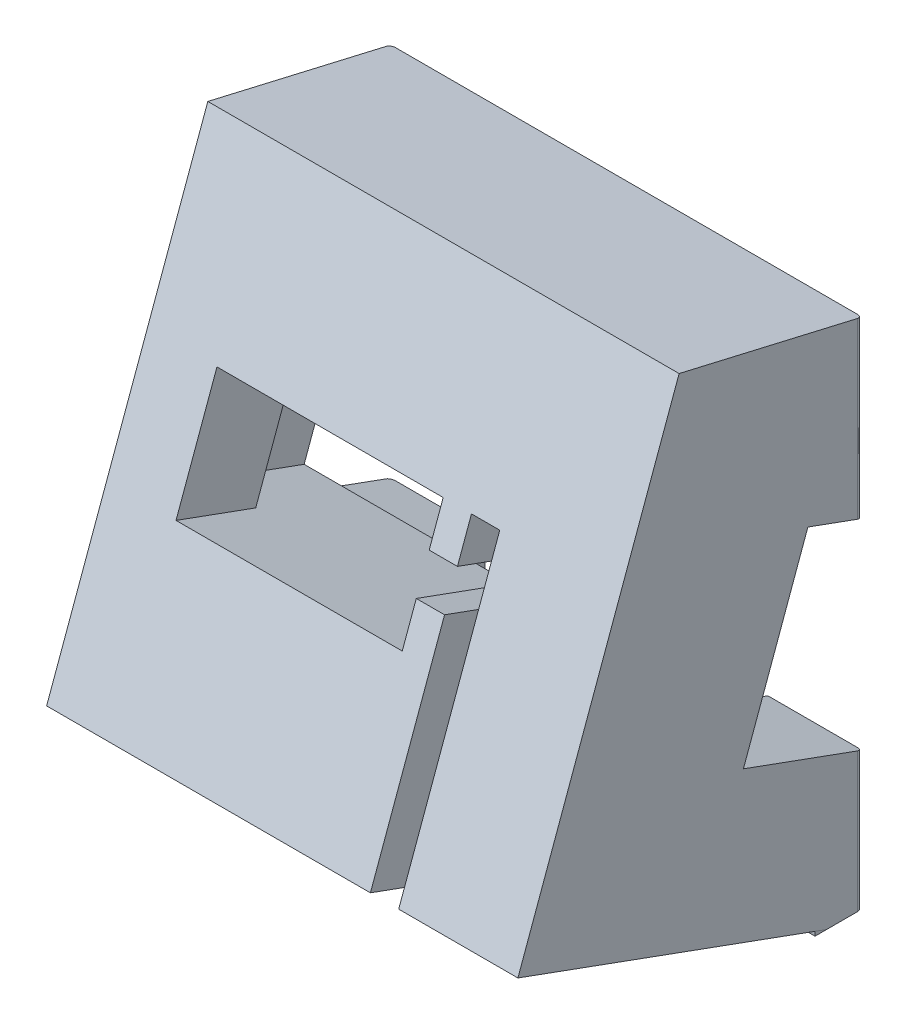
SolidWorks part; units mm, degrees
ref_plane "Front Plane" through (0, 0, 0) normal (0, 0, 1) x (1, 0, 0)
ref_plane "Top Plane" through (0, 0, 0) normal (0, 1, 0) x (1, 0, 0)
ref_plane "Right Plane" through (0, 0, 0) normal (1, 0, 0) x (0, 0, -1)
sketch "Sketch2" plane through (0, 0, 0) normal (0, 0, 1) x (1, 0, 0)
  line L0 (-100, -75) -> (-100, -45)
  line L1 (-100, 75) -> (100, 75)
  line L2 (-100, 75) -> (-100, -75)
  line L3 (-100, -75) -> (100, -75)
  line L4 (100, 75) -> (100, -75)
  line L5 (-100, 75) -> (100, -75) construction
  line L6 (-100, -75) -> (100, 75) construction
  line L7 (-100, -45) -> (-60, -45)
  line L8 (-60, -45) -> (-60, -75)
  line L9 (100, -75) -> (100, -45)
  line L10 (100, -45) -> (60, -45)
  line L11 (60, -45) -> (60, -75)
  line L12 (-60, -75) -> (-60, -65)
  line L13 (-60, -65) -> (60, -65)
  line L14 (-60, -45) -> (-50, -45)
  line L15 (-50, -45) -> (-50, -55)
  line L16 (-50, -55) -> (-60, -55)
  line L17 (60, -45) -> (50, -45)
  line L18 (50, -45) -> (50, -55)
  line L19 (50, -55) -> (60, -55)
  line L20 (-55, -55) -> (-55, -50)
  line L21 (-55, -50) -> (-50, -50)
  line L22 (-50, -45) -> (-52, -45)
  line L23 (-50, -45) -> (-50, -47)
  line L24 (0, -65) -> (0, -61.3332)
  line L25 (-58, -53) -> (-52, -53)
  line L26 (-58, -53) -> (-58, -47)
  line L27 (-58, -47) -> (-52, -47)
  line L28 (-52, -53) -> (-52, -47)
  line L29 (-58, -53) -> (-52, -47) construction
  line L30 (-58, -47) -> (-52, -53) construction
  line L31 (58, -47) -> (52, -47)
  line L32 (52, -53) -> (52, -47)
  line L33 (58, -53) -> (52, -53)
  line L34 (58, -53) -> (58, -47)
  point P0 (0, 0)
  dimension "D1" = 200
  dimension "D2" = 150
  dimension "D3" = 40
extrude "Boss-Extrude1" add sketch "Sketch2" along normal blind 5 contours L19 L18 L17 L10 L4 L1 L2 L7 L14 L15 L16 L8 L13 L11 | L18 L19 L11 L17 L34 L33 L32 L31 | L28 L21 L15 L14 L8 L16 L20 L25 L26 L27 | L28 L25 L20 L16 L15 L21 region at (0, 9.084, 0) region at (-56, -45.1414, 0) region at (-51.9375, -53.0625, 0) region at (55, -54.8586, 0)
sketch "Sketch3" plane through (0, 0, 5) normal (0, 0, 1) x (1, 0, 0)
  line L0 (-100, 75) -> (-100, -45) construction
  line L1 (-100, 75) -> (-100, 55)
  line L2 (-100, 55) -> (100, 55)
  line L3 (100, 75) -> (100, -45) construction
  line L4 (100, 55) -> (100, 75)
  line L5 (100, 75) -> (-100, 75)
extrude "Cut-Extrude1" cut sketch "Sketch3" against normal blind 5
sketch "Sketch4" plane through (0, 0, 0) normal (0, 0, -1) x (-1, 0, 0)
  line L0 (-100, 55) -> (100, 55)
  line L1 (100, 55) -> (100, -45)
  line L2 (100, -45) -> (-100, -45)
  line L3 (-100, -45) -> (-100, 55)
  line L4 (100, 55) -> (95, 55)
  line L5 (95, 55) -> (95, -45)
  line L6 (95, -45) -> (100, -45)
  line L7 (100, 55) -> (100, 45)
  line L8 (100, 45) -> (95, 45)
  line L9 (95, 45) -> (95, 50)
  line L10 (95, 50) -> (100, 50)
  line L11 (100, 50) -> (99, 50)
  line L12 (100, 50) -> (100, 49)
  line L13 (97.5, 45) -> (97.5, 47.5)
  line L14 (100, 5) -> (95, 5)
  line L15 (96, 46) -> (99, 46)
  line L16 (96, 46) -> (96, 49)
  line L17 (96, 49) -> (99, 49)
  line L18 (99, 46) -> (99, 49)
  line L19 (96, 46) -> (99, 49) construction
  line L20 (96, 49) -> (99, 46) construction
  line L21 (96, -39) -> (99, -39)
  line L22 (99, -36) -> (99, -39)
  line L23 (96, -36) -> (99, -36)
  line L24 (96, -36) -> (96, -39)
  line L25 (100, 5) -> (100, 7.5)
  line L26 (100, 5) -> (100, 2.5)
  line L27 (100, 2.5) -> (95, 2.5)
  line L28 (95, 2.5) -> (95, 7.5)
  line L29 (95, 7.5) -> (100, 7.5)
  line L30 (100, 2.5) -> (99, 2.5)
  line L31 (100, 2.5) -> (100, 3.5)
  line L32 (0, -45) -> (0, -36)
  line L33 (96, 6.5) -> (99, 6.5)
  line L34 (96, 6.5) -> (96, 3.5)
  line L35 (96, 3.5) -> (99, 3.5)
  line L36 (99, 6.5) -> (99, 3.5)
  line L37 (96, 6.5) -> (99, 3.5) construction
  line L38 (96, 3.5) -> (99, 6.5) construction
  line L39 (97.5, -36) -> (97.5, -39)
  line L40 (100, 50) -> (95, 50)
  line L41 (100, 50) -> (100, 45)
  line L42 (100, 45) -> (95, 45)
  line L43 (95, 50) -> (95, 45)
  line L44 (100, 50) -> (95, 45) construction
  line L45 (100, 45) -> (95, 50) construction
  line L46 (97.5, -39) -> (97.5, -40)
  line L47 (-100, 45) -> (-95, 45)
  line L48 (100, -35) -> (95, -35)
  line L49 (100, -35) -> (100, -40)
  line L50 (100, -40) -> (95, -40)
  line L51 (95, -35) -> (95, -40)
  line L52 (100, -35) -> (95, -40) construction
  line L53 (100, -40) -> (95, -35) construction
  line L54 (-95, 50) -> (-95, 45)
  line L55 (-100, 50) -> (-95, 50)
  line L56 (-100, 50) -> (-100, 45)
  line L57 (-100, 5) -> (-100, 7.5)
  line L58 (-95, 7.5) -> (-100, 7.5)
  line L59 (-95, 2.5) -> (-95, 7.5)
  line L60 (-100, 2.5) -> (-95, 2.5)
  line L61 (-100, 5) -> (-100, 2.5)
  line L62 (-100, -40) -> (-95, -40)
  line L63 (-95, -35) -> (-95, -40)
  line L64 (-100, -35) -> (-95, -35)
  line L65 (-100, -35) -> (-100, -40)
  point P31 (97.5, 5)
  point P44 (97.5, -37.5)
  line M38 (-100, 55) -> (-100, -45)
extrude "Cut-Extrude2" cut sketch "Sketch4" against normal blind 5 contours L55 L3 L47 L54 | L3 L60 L59 L58 M38 | L64 L3 L62 L63 | L18 L15 L8 L1 L7 L10 L5 L16 L17 | L15 L18 L17 L16 | L33 L36 L14 L1 L29 L5 L34 | L14 L36 L35 L34 L5 L27 L1 L26 | L36 L14 L34 L35 | L36 L33 L34 L14 | L50 L1 L48 L5 L21 L24 L23 L22 | L23 L39 L21 L22 | L39 L23 L24 L21 region at (97.5, 47.5, 0) region at (-96.75, 46.0424, 0) region at (-97, 49.9293, 0) region at (97.5, 5, 0) region at (-97.5, 6.5313, 0) region at (-97.5, 3.4688, 0) region at (-97.5, 5.75, 0) region at (-97.5, 4.25, 0) region at (97.5, -37.5, 0) region at (-96.75, -37.5, 0) region at (-98.25, -37.5, 0) region at (-97.5, -35.0707, 0)
sketch "Sketch6" plane through (0, 0, 0) normal (0, 0, -1) x (-1, 0, 0)
  line L0 (0, -65) -> (0, -45)
  line L1 (60, -65) -> (-60, -65) construction
  line L2 (0, -45) -> (50, -45)
  line L3 (50, -45) -> (50, -65)
  line L4 (0, -45) -> (-50, -45)
  line L5 (-50, -45) -> (-50, -65)
  line L6 (-50, -45) -> (-60, -45)
  line M21 (-60, -65) -> (60, -65)
extrude "Boss-Extrude2" add sketch "Sketch6" along normal blind 100 contours L3 L2 L0 M21 | L4 L5 L0 M21 region at (25, -55, 0) region at (-25, -55, 0)
sketch "Sketch8" plane through (50, 0, 0) normal (1, 0, 0) x (0, 0, -1)
  line L0 (100, -45) -> (100, 55)
  line L1 (100, 55) -> (78.5761, 55)
  line L2 (100, -45) -> (42.1791, -45)
  line L3 (100, -45) -> (0, -45) construction
  line L4 (78.5761, 55) -> (42.1791, -45)
  line L5 (60.3776, 5) -> (63.7978, 14.3969)
  line L6 (60.3776, 5) -> (56.9574, -4.3969)
  line M8 (100, -45) -> (0, -45)
  dimension "D1" = 21.4239
  dimension "D2" = 57.8209
extrude "Boss-Extrude3" add sketch "Sketch8" against normal blind 100 contours L1 L4 L0 M8 region at (50, -2.655, -78.7957)
sketch "Sketch12" plane through (50, 0, 0) normal (1, 0, 0) x (0, 0, -1)
  line L0 (42.1791, -45) -> (78.5761, 55)
  line L2 (42.1791, -45) -> (100, -45)
  line L3 (100, 55) -> (100, -65) construction
  line L4 (100, -45) -> (100, 55)
  line L5 (78.5761, 55) -> (83.897, 55)
  line L6 (100, 55) -> (78.5761, 55) construction
  line L7 (83.897, 55) -> (88.897, 55)
  line L8 (83.897, 55) -> (47.5, -45)
  line L9 (88.897, 55) -> (52.5, -45)
  line M5 (100, 55) -> (78.5761, 55)
  line M6 (78.5761, 55) -> (42.1791, -45)
  dimension "D1" = 5.3209
extrude "Cut-Extrude4" cut sketch "Sketch12" against normal blind 100 contours L8 L2 M5 M6 region at (50, 5, -63.0381)
sketch "Sketch13" plane through (0, -20.5302, -56.4063) normal (0, 0.342, 0.9397) x (1, 0, 0)
  line L0 (-50, 80.3776) -> (50, 80.3776)
  line L1 (50, 80.3776) -> (50, -26.0402)
  line L2 (50, -26.0402) -> (-50, -26.0402)
  line L3 (-50, -26.0402) -> (-50, 80.3776)
  line L4 (0, 80.3776) -> (0, 27.1687)
  circle A0 centre (0, 27.1687) radius 10
extrude "Boss-Extrude5" add sketch "Sketch13" along normal blind 100 contours A0 region at (6.8711, 11.4567, -68.0486)
sketch "Sketch14" plane through (0, 13.6718, 37.563) normal (0, 0.342, 0.9397) x (1, 0, 0)
  circle A0 centre (0, 27.1687) radius 10.3
  circle A1 centre (0, 27.1687) radius 12.5
  circle M3 centre (0, 27.1687) radius 10
  dimension "D1" = 25
extrude "Cut-Extrude5" cut sketch "Sketch14" against normal blind 100 contours M3 | A1 M3 | A0 M3 | A0 | A1 region at (-10.0087, 39.202, 28.2708) region at (-12.1464, 39.202, 28.2708) region at (0, 39.202, 28.2708)
ref_plane "Plane1" through (0, 13.6718, 37.563) normal (0, 0.342, 0.9397) x (1, 0, 0)
sketch "Sketch15" plane through (0, 13.6718, 37.563) normal (0, 0.342, 0.9397) x (1, 0, 0)
  circle A0 centre (0, 27.1687) radius 10
  circle A1 centre (0, 27.1687) radius 12.5
  circle A2 centre (0, 27.1687) radius 15
ref_plane "Plane2" through (0, 0, -30) normal (0, 0, -1) x (-1, 0, 0)
extrude "Boss-Extrude6" add sketch "Sketch15" against normal blind 40 contours A2 A1 region at (-14.5757, 39.202, 28.2708)
sketch "Sketch16" plane through (0, 0, -30) normal (0, 0, -1) x (-1, 0, 0)
  line L0 (0, 61.0723) -> (0, 0)
  line L1 (0, 0) -> (25, 0)
  line L2 (25, 0) -> (25, 61.0723)
  line L3 (25, 61.0723) -> (-25, 61.0723)
  line L4 (-25, 61.0723) -> (-25, 0)
  line L5 (-25, 0) -> (0, 0)
sketch "Sketch17" plane through (0, 13.6718, 37.563) normal (0, 0.342, 0.9397) x (1, 0, 0)
  circle A0 centre (0, 27.1687) radius 10.3
  circle A1 centre (0, 27.1687) radius 12.5
extrude "Cut-Extrude10" cut sketch "Sketch16" against normal blind 35 contours L4 L5 L0 L3 | L2 L3 L0 L1 region at (-12.5, 30.5361, -30) region at (12.5, 30.5361, -30)
sketch "Sketch18" plane through (0, 0, 5) normal (0, 0, 1) x (1, 0, 0)
  line L0 (25, 55) -> (25, 0)
  line L1 (25, 0) -> (-25, 0)
  line L2 (-25, 0) -> (-25, 55)
  line L3 (-25, 55) -> (25, 55)
  line L4 (-30, 55) -> (-30, 60)
  line L5 (30, 0) -> (30, 55)
  line L6 (25, 55) -> (100, 55) construction
  line L7 (30, 55) -> (25, 55)
  line L8 (30, 0) -> (30, -5)
  line L9 (30, -5) -> (-30, -5)
  line L10 (-30, -5) -> (-30, 55)
  line L11 (-100, 55) -> (-25, 55) construction
  line L12 (-30, 55) -> (-25, 55)
  line L13 (-30, 60) -> (30, 60)
  line L14 (30, 60) -> (30, 55)
  line L15 (-30, 55) -> (30, 55)
  line M5 (25, 55) -> (25, 0)
  line M6 (25, 0) -> (-25, 0)
  line M7 (-25, 0) -> (-25, 55)
  line M8 (-25, 55) -> (-100, 55)
  line M40 (100, 55) -> (25, 55)
sketch "Sketch20" plane through (0, 0, 5) normal (0, 0, -1) x (-1, 0, 0)
  ellipse E2 centre (0, 30.7322) end of major axis (0, 44.0344) minor radius 12.5 (0, 44.0344) -> (0, 44.0344) ccw
  ellipse E3 centre (0, 30.7322) end of major axis (0, 44.0344) minor radius 12.5
  ellipse E5 centre (0, 30.7322) end of major axis (0, 46.6948) minor radius 15 (0, 46.6948) -> (0, 46.6948) ccw
  ellipse E6 centre (0, 30.7322) end of major axis (0, 46.6948) minor radius 15
  dimension "D1" = 0
  dimension "D2" = 0
sketch "Sketch21" plane through (0, 0, -30) normal (0, 0, -1) x (-1, 0, 0)
  line L0 (0, 30.7322) -> (0, 46.6948)
  line L1 (0, 46.6948) -> (-15, 46.6948)
  line L2 (-15, 46.6948) -> (-15, 14.7695)
  line L3 (-15, 14.7695) -> (15, 14.7695)
  line L4 (15, 14.7695) -> (15, 46.6948)
  line L5 (15, 46.6948) -> (0, 46.6948)
  line L6 (-25, 55) -> (-25, 0)
  line L7 (-25, 0) -> (25, 0)
  line L8 (25, 0) -> (25, 55)
  line L9 (25, 55) -> (-25, 55)
  line L10 (-30, 55) -> (-30, 60)
  line L11 (-30, 60) -> (-25, 60)
  line L12 (-25, 60) -> (30, 60)
  line L13 (30, 60) -> (30, 55)
  line L14 (30, 55) -> (30, -5)
  line L15 (30, -5) -> (-30, -5)
  line L16 (-30, -5) -> (-30, 55)
  line L17 (-25, 55) -> (-30, 55)
  line L18 (25, 55) -> (30, 55)
  line L19 (-25, 55) -> (25, 55)
  ellipse E2 centre (0, 30.7322) end of major axis (0, 46.6948) minor radius 15
  ellipse E3 centre (0, 30.7322) end of major axis (0, 46.6948) minor radius 15
  ellipse E5 centre (0, 30.7322) end of major axis (0, 44.0344) minor radius 12.5
  ellipse E6 centre (0, 30.7322) end of major axis (0, 44.0344) minor radius 12.5
  dimension "D1" = 0
  dimension "D2" = 0
extrude "Cut-Extrude11" cut sketch "Sketch15<4>" against normal blind 15 contours A2 A1 region at (-14.5757, 39.202, 28.2708)
sketch "Sketch15<4>" plane through (0, 13.6718, 37.563) normal (0, 0.342, 0.9397) x (1, 0, 0) same geometry as "Sketch15"
sketch "Sketch22" plane through (0, 0, 0) normal (0, 0, -1) x (-1, 0, 0)
  line L0 (30, -5) -> (-30, -5)
  line L1 (-30, -5) -> (-30, 60)
  line L2 (-30, 60) -> (30, 60)
  line L3 (30, 60) -> (30, -5)
  line L4 (25, 0) -> (-25, 0)
  line L5 (-25, 0) -> (-25, 55)
  line L6 (-25, 55) -> (25, 55)
  line L7 (25, 55) -> (25, 0)
  line L8 (-25, 55) -> (-30, 55)
  line L9 (-25, 55) -> (-100, 55) construction
  line L10 (25, 55) -> (30, 55)
  line L11 (30, -5) -> (30, 55) construction
  line L12 (25, 0) -> (30, 0)
  line L13 (-25, 0) -> (-30, 0)
  line M17 (25, 0) -> (-25, 0)
  line M18 (-25, 0) -> (-25, 55)
  line M56 (25, 55) -> (25, 0)
extrude "Boss-Extrude7" add sketch "Sketch18" along normal blind 5 contours L10 L9 L8 L5 M40 M5 M6 M7 M8 region at (27.5, 54.1515, 5)
sketch "Sketch23" plane through (0, 8.5415, 23.4676) normal (0, 0.342, 0.9397) x (1, 0, 0)
  circle A0 centre (0, 27.1687) radius 15
  circle A1 centre (0, 27.1687) radius 10.3
  circle A2 centre (0, 27.1687) radius 12.5
  circle M4 centre (0, 27.1687) radius 12.5
  circle M5 centre (0, 27.1687) radius 15
extrude "Boss-Extrude8" add sketch "Sketch23" against normal blind 25 contours M5 M4 region at (-14.5757, 34.0717, 14.1754)
extrude "Cut-Extrude12" cut sketch "Sketch21" against normal blind 35 contours E6 E3 | E6 | L8 L9 L6 L7 L5 L4 L3 L2 L1 | E3 L4 L5 | E3 L1 L2 | E3 L2 L3 | E3 L3 L4 region at (-10.4462, 41.5478, -30) region at (11.6495, 43.1293, -30) region at (-11.6495, 43.1293, -30) region at (0, 17.795, -30) region at (11.6495, 18.335, -30) region at (-11.6495, 18.335, -30) region at (0, 54.2567, -30)
extrude "Boss-Extrude9" add sketch "Sketch22" against normal blind 5 contours L6 M18 M17 M56 region at (0, 27.5, 0)
extrude "Cut-Extrude13" cut sketch "Sketch23<3>" against normal blind 20 contours A1 M4 | A1 region at (0, 34.0717, 14.1754) region at (-12.1464, 34.0717, 14.1754)
sketch "Sketch23<3>" plane through (0, 8.5415, 23.4676) normal (0, 0.342, 0.9397) x (1, 0, 0) same geometry as "Sketch23"
sketch "Sketch27" plane through (0, 8.5415, 23.4676) normal (0, 0.342, 0.9397) x (1, 0, 0)
  line L1 (-2, 42.1687) -> (2, 42.1687)
  line L2 (-2, 42.1687) -> (-2, 12.1687)
  line L3 (-2, 12.1687) -> (2, 12.1687)
  line L4 (2, 42.1687) -> (2, 12.1687)
  line L5 (-2, 42.1687) -> (2, 12.1687) construction
  line L6 (-2, 12.1687) -> (2, 42.1687) construction
  line L7 (-15, 29.1687) -> (15, 29.1687)
  line L8 (-15, 29.1687) -> (-15, 25.1687)
  line L9 (-15, 25.1687) -> (15, 25.1687)
  line L10 (15, 29.1687) -> (15, 25.1687)
  line L11 (-15, 29.1687) -> (15, 25.1687) construction
  line L12 (-15, 25.1687) -> (15, 29.1687) construction
  circle A0 centre (0, 27.1687) radius 12.5
  circle A1 centre (0, 27.1687) radius 15
  point P0 (0, 27.1687)
  point P6 (0, 27.1687)
  circle M8 centre (0, 27.1687) radius 12.5
  circle M9 centre (0, 27.1687) radius 15
  dimension "D1" = 4
  dimension "D2" = 4
  dimension "D3" = 30
  dimension "D4" = 30
extrude "Cut-Extrude15" cut sketch "Sketch27" against normal blind 3 contours L4 L2 M9 M8 | L9 L7 M8 M9 | L9 L7 M9 M8 | L4 L2 M8 M9 region at (0, 46.9463, 9.4894) region at (-13.7008, 34.0717, 14.1754) region at (13.7008, 34.0717, 14.1754) region at (0, 21.1972, 18.8613)
sketch "Sketch28" plane through (0, 0, 10) normal (0, 0, 1) x (1, 0, 0)
  line L0 (-25, 55) -> (-25, 5)
  line L1 (-25, 55) -> (-25, 0) construction
  line L2 (-25, 5) -> (25, 5)
  line L3 (25, 55) -> (25, 0) construction
  line L4 (25, 5) -> (25, 0)
  line L5 (25, 0) -> (-25, 0)
  line L6 (-25, 0) -> (-25, 5)
  line L7 (-25, 0) -> (-30, 0)
  line L8 (-30, -5) -> (-30, 55) construction
  line L9 (-30, 0) -> (-30, -5)
  line L10 (-30, -5) -> (30, -5)
  line L11 (30, -5) -> (30, 0)
  line L12 (30, 55) -> (30, -5) construction
  line L13 (30, 0) -> (25, 0)
  line M1 (-30, 55) -> (-30, -5)
  line M2 (-30, -5) -> (30, -5)
  line M3 (30, -5) -> (30, 55)
  line M5 (25, 55) -> (25, 0)
  line M6 (25, 0) -> (-25, 0)
  line M7 (-25, 0) -> (-25, 55)
extrude "Cut-Extrude16" cut sketch "Sketch28" against normal blind 5 contours L13 L7 M3 M6 M1 M2 region at (0, -2.5, 10)
extrude "Boss-Extrude12" add sketch "Sketch28<3>" against normal blind 5 contours L2 M7 M6 M5 region at (0, 2.5, 10)
sketch "Sketch28<3>" plane through (0, 0, 10) normal (0, 0, 1) x (1, 0, 0) same geometry as "Sketch28"
sketch "Sketch31" plane through (0, 8.5415, 23.4676) normal (0, 0.342, 0.9397) x (1, 0, 0)
  line L0 (0, 33.5187) -> (6.35, 33.5187)
  line L1 (6.35, 33.5187) -> (6.35, 27.1687)
  line L2 (6.35, 27.1687) -> (6.35, 20.8187)
  line L3 (6.35, 20.8187) -> (0, 20.8187)
  line L4 (6.35, 33.5187) -> (-17.65, 33.5187)
  line L5 (-17.65, 33.5187) -> (-17.65, 20.8187)
  line L6 (-17.65, 20.8187) -> (6.35, 20.8187)
  line L7 (-17.65, 33.5187) -> (-22.85, 33.5187)
  line L8 (-22.85, 33.5187) -> (-22.85, 20.8187)
  line L9 (-22.85, 20.8187) -> (-17.65, 20.8187)
  line L10 (6.35, 33.5187) -> (11.55, 33.5187)
  line L11 (11.55, 33.5187) -> (11.55, 20.8187)
  line L12 (11.55, 20.8187) -> (6.35, 20.8187)
  line L14 (-25, 52.1687) -> (25, 52.1687)
  line L15 (-25, 52.1687) -> (-25, 2.1687)
  line L16 (-25, 2.1687) -> (25, 2.1687)
  line L17 (25, 52.1687) -> (25, 2.1687)
  line L18 (-25, 52.1687) -> (25, 2.1687) construction
  line L19 (-25, 2.1687) -> (25, 52.1687) construction
  circle A0 centre (0, 27.1687) radius 2.5
  circle A1 centre (0, 27.1687) radius 6.35
  arc M3 (14.8661, 29.1687) -> (2, 42.0347) centre (0, 27.1687) ccw
  line M4 (2, 42.0347) -> (2, 39.5076)
  arc M5 (2, 39.5076) -> (12.339, 29.1687) centre (0, 27.1687) cw
  line M6 (12.339, 29.1687) -> (14.8661, 29.1687)
  dimension "D1" = 5
  dimension "D2" = 6.35
  dimension "D3" = 50
  dimension "D4" = 50
extrude "Boss-Extrude13" add sketch "Sketch31" along normal blind 20 contours L17 L14 L15 L16 L11 L12 L3 L6 L9 L8 L7 L4 L0 L10 M5 M4 M3 M6 | L10 L11 M5 M6 M3 M4 | L12 L11 L10 L1 L2 M5 | L11 L10 M5 | L8 L9 L5 L7 region at (8.9293, 34.0232, 14.193) region at (-20.25, 34.0717, 14.1754) region at (9.074, 42.6669, 11.047) region at (11.2964, 39.562, 12.1771) region at (0, 56.8996, 5.8667)
extrude "Cut-Extrude17" cut sketch "Sketch31<5>" along normal blind 11 contours L12 L11 L10 L1 L2 M5 | L11 L10 M5 | L8 L9 L5 L7 region at (8.9293, 34.0232, 14.193) region at (-20.25, 34.0717, 14.1754) region at (11.2964, 39.562, 12.1771)
sketch "Sketch31<5>" plane through (0, 8.5415, 23.4676) normal (0, 0.342, 0.9397) x (1, 0, 0) same geometry as "Sketch31"
sketch "Sketch32" plane through (0, 15.3819, 42.2614) normal (0, 0.342, 0.9397) x (1, 0, 0)
  line L0 (6.35, 33.5187) -> (11.55, 33.5187)
  line L1 (11.55, 33.5187) -> (11.55, 20.8222)
  line L2 (6.35, 20.8187) -> (11.55, 20.8222)
  line L3 (6.35, 27.1687) -> (6.35, 29.1687)
  line L4 (6.35, 33.5187) -> (6.35, 20.8187) construction
  line L5 (6.35, 29.1687) -> (9.35, 29.1687)
  line L6 (9.35, 29.1687) -> (9.35, 25.1687)
  line L7 (9.35, 25.1687) -> (6.35, 25.1687)
  line L8 (6.35, 25.1687) -> (6.35, 27.1687)
  line M6 (6.35, 33.5187) -> (6.35, 20.8187)
extrude "Cut-Extrude18" cut sketch "Sketch32" against normal blind 9 contours L7 L6 L5 M6 region at (7.85, 40.9121, 32.9692)
sketch "Sketch33" plane through (-25, 0, 0) normal (-1, 0, 0) x (0, 0, 1)
  line L0 (5.6249, 57.564) -> (24.4187, 64.4044)
  line L1 (24.4187, 64.4044) -> (41.5197, 17.4198)
  line L2 (41.5197, 17.4198) -> (22.7259, 10.5794)
  line L3 (22.7259, 10.5794) -> (5.6249, 57.564)
  line L4 (24.4187, 64.4044) -> (0, 64.4044)
  line L5 (0, 64.4044) -> (0, 55)
  line L6 (0, 64.4044) -> (-5, 64.4044)
  line L7 (-5, 64.4044) -> (-5, 55)
  line L8 (-5, 55) -> (6.5581, 55)
  line L9 (-5, 55) -> (-5, 45)
  line L10 (-5, 45) -> (0, 45)
  line L11 (0, 45) -> (0, 55)
  line L12 (5, 55) -> (5, 5.5)
  line L13 (5, 7.5) -> (5, 2.5) construction
  line L14 (5, 5.5) -> (41.5197, 5.5)
  line L15 (41.5197, 5.5) -> (41.5197, 17.4198)
  line L16 (5.6249, 57.564) -> (10.7552, 43.4686)
  line L17 (22.7259, 10.5794) -> (17.5956, 24.6748)
  line L18 (17.5956, 24.6748) -> (5, 20.0904)
  line L19 (5, 20.0904) -> (5, 5.5)
  line L20 (10.7552, 43.4686) -> (5, 41.3739)
sketch "Sketch34" plane through (0, 0, -100) normal (0, 0, -1) x (-1, 0, 0)
  line L0 (-100, 55) -> (100, 55)
  line L1 (100, 55) -> (100, -65)
  line L2 (100, -65) -> (-100, -65)
  line L3 (-100, -65) -> (-100, 55)
  line L4 (0, 55) -> (30, 55)
  line L5 (30, 55) -> (30, 5)
  line L6 (0, 55) -> (-30, 55)
  line L7 (-30, 55) -> (-30, 5)
  line L9 (30, 5) -> (30, 0)
  line L10 (30, 0) -> (25, 0)
  line L11 (-30, 0) -> (-30, 5)
  line L12 (-30, 55) -> (-25, 55)
  line L13 (-25, 55) -> (-25, 5)
  line L14 (30, 0) -> (25, 0)
  line L15 (25, 5) -> (25, 55)
  line L16 (-25, 0) -> (-30, 0)
  line L17 (30, 55) -> (25, 55)
  line L18 (-25, 0) -> (25, 0)
  line L19 (-30, 5) -> (30, 5)
  line M5 (50, -65) -> (50, 55)
  line M6 (50, 55) -> (-50, 55)
  line M7 (-50, 55) -> (-50, -65)
  line M8 (-50, -65) -> (50, -65)
extrude "Cut-Extrude19" cut sketch "Sketch34" against normal blind 105 contours L18 L16 L11 L7 L0 L5 L9 L10 M7 M8 M5 M6 | L2 L1 L0 M5 | L3 L2 L0 M7 | L13 L19 L15 L4 M6 region at (75, -5, -100) region at (0, -17.3276, -100) region at (0, 30, -100) region at (-75, -5, -100)
extrude "Cut-Extrude20" cut sketch "Sketch34<3>" against normal blind 110 contours L7 L19 L13 L6 | L19 L11 L16 L18 L10 L9 | L15 L19 L5 L0 region at (27.5, 30, -100) region at (0, 2.5, -100) region at (-27.5, 30, -100)
sketch "Sketch34<3>" plane through (0, 0, -100) normal (0, 0, -1) x (-1, 0, 0) same geometry as "Sketch34"
sketch "Sketch35" plane through (0, 8.5415, 23.4676) normal (0, -0.342, -0.9397) x (-1, 0, 0)
  line L0 (22.85, 33.5187) -> (22.85, 20.8187)
sketch "Sketch36" plane through (25, 0, 0) normal (1, 0, 0) x (0, 0, -1)
  line L0 (-24.4187, 64.4044) -> (-5.6249, 57.564)
  line L1 (-5.6249, 57.564) -> (-22.7259, 10.5794)
  line L2 (-22.7259, 10.5794) -> (-41.5197, 17.4198)
  line L3 (-41.5197, 17.4198) -> (-24.4187, 64.4044)
  line L4 (-24.4187, 64.4044) -> (5, 57.564)
  line L6 (5, 57.564) -> (5, 55)
  line L7 (5, 55) -> (0, 55)
  line L9 (5, 55) -> (5, 45)
  line L10 (5, 45) -> (0, 45)
  line L11 (0, 45) -> (0, 55)
  line L12 (-5, 55) -> (0, 55)
  line L13 (-5, 55) -> (-6.5581, 55)
  line L14 (-5, 55) -> (-5, 41.3739)
  line L15 (-5, 41.3739) -> (-10.7552, 43.4686)
  line L16 (-5, 41.3739) -> (-5, 20.0904)
  line L17 (-5, 20.0904) -> (-5, 5.5)
  line L18 (-5, 5.5) -> (-8.7703, 5.5)
  line L20 (-5, 20.0904) -> (-5, 41.3739)
  line L21 (-5, 20.0904) -> (-17.5956, 24.6748)
  line L22 (-22.7259, 10.5794) -> (-8.7703, 5.5)
  point P9 (0, 55)
  line M6 (-22.7259, 10.5794) -> (-5.6249, 57.564)
  line M7 (-5.6249, 57.564) -> (-24.4187, 64.4044)
ref_plane "Plane3" through (0, 1.7011, 4.6737) normal (0, -0.342, -0.9397) x (-1, 0, 0)
sketch "Sketch38" plane through (0, 1.7011, 4.6737) normal (0, -0.342, -0.9397) x (-1, 0, 0)
  circle A2 centre (0, 27.1687) radius 15
  circle A3 centre (0, 27.1687) radius 15
  circle A5 centre (0, 27.1687) radius 12.5
  circle A6 centre (0, 27.1687) radius 12.5
  dimension "D1" = 0
  dimension "D2" = 0
extrude "Cut-Extrude21" cut sketch "Sketch38" against normal blind 20
sketch "Sketch39" plane through (0, 15.3819, 42.2614) normal (0, 0.342, 0.9397) x (1, 0, 0)
  line L0 (6.35, 20.8187) -> (6.35, 25.1687)
  line L1 (6.35, 25.1687) -> (9.35, 25.1687)
  line L2 (9.35, 25.1687) -> (9.35, 2.1687)
  line L3 (-25, 2.1687) -> (25, 2.1687) construction
  line L4 (9.35, 2.1687) -> (6.35, 2.1687)
  line L5 (6.35, 2.1687) -> (6.35, 20.8187)
  line L6 (6.35, 20.8187) -> (9.35, 20.8187)
  line L7 (9.35, 25.1687) -> (9.35, 29.1687)
  line L8 (9.35, 29.1687) -> (12.35, 29.1687)
  line L9 (12.35, 29.1687) -> (12.35, 2.1687)
  line L10 (12.35, 2.1687) -> (9.35, 2.1687)
  line L11 (9.35, 29.1687) -> (9.35, 2.1687)
  line L12 (6.35, 29.1687) -> (6.35, 33.5187)
  line L13 (9.35, 29.1687) -> (9.35, 33.5187)
  line L14 (9.35, 33.5187) -> (12.35, 33.5187)
  line L15 (12.35, 33.5187) -> (12.35, 29.1687)
  line M9 (-25, 2.1687) -> (25, 2.1687)
  line M10 (9.35, 29.1687) -> (9.35, 25.1687)
extrude "Cut-Extrude23" cut sketch "Sketch39" against normal blind 20 contours L9 L8 L2 M10 M9 | L15 L14 L13 L8 region at (10.85, 30.1056, 36.9024) region at (10.85, 44.8353, 31.5413)
extrude "Boss-Extrude15" add sketch "Sketch36" against normal blind 50 contours L13 L12 L7 L6 L4 L1 M7 | L11 L10 L9 L7 | L15 L14 L13 L1 | L22 L18 L17 L21 M6 region at (25, 58.2724, 4.924) region at (25, 47.4608, 7.0152) region at (25, 14.5458, 12.7218) region at (25, 50, -2.5)
sketch "Sketch42" plane through (0, 2.0379, -0.7417) normal (0, -0.9397, 0.342) x (1, 0, 0)
  line L0 (-15, 24.9737) -> (15, 24.9737)
  line L1 (15, 24.9737) -> (-15, 24.9737) construction
  line L2 (15, 24.9737) -> (15, 6.5796)
  line L3 (-25, 6.5796) -> (25, 6.5796) construction
  line L4 (15, 6.5796) -> (-15, 6.5796)
  line L5 (-15, 6.5796) -> (-15, 24.9737)
extrude "Cut-Extrude24" cut sketch "Sketch42" against normal blind 55
sketch "Sketch43" plane through (-25, 0, 0) normal (-1, 0, 0) x (0, 0, 1)
  line L0 (5, 55) -> (5, 64.4044)
  line L1 (24.4187, 64.4044) -> (0, 64.4044) construction
  line L2 (5, 64.4044) -> (-5, 64.4044)
  line L3 (-5, 64.4044) -> (-5, 45)
  line L4 (-5, 45) -> (5, 45)
  line L5 (5, 46.6948) -> (5, 14.7695) construction
  line L6 (5, 45) -> (5, 55)
extrude "Cut-Extrude25" cut sketch "Sketch43" against normal blind 55
sketch "Sketch44" plane through (0, 0, 5) normal (0, 0, -1) x (-1, 0, 0)
  line L12 (-25, 64.4044) -> (25, 64.4044)
fillet "Fillet1" radius 0.5 4 edges at (-25, 50.6316, 5) (-25, 12.7952, 5) (25, 12.7952, 5) (25, 50.6316, 5)
sketch "Sketch45" plane through (-25, 0, 0) normal (-1, 0, 0) x (0, 0, 1)
  line L0 (5, 5.5) -> (10, 5.5)
  line L1 (5, 5.5) -> (41.5197, 5.5) construction
  line L2 (10, 5.5) -> (10, 5.9476)
  line L3 (41.5197, 17.4198) -> (8.7703, 5.5) construction
  line L4 (10, 5.9476) -> (8.7703, 5.5)
  line M11 (8.7703, 5.5) -> (41.5197, 17.4198)
extrude "Boss-Extrude16" add sketch "Sketch45" against normal blind 10 contours L0 L2 M11 region at (-25, 5.6492, 9.5901)
sketch "Sketch46" plane through (25, 0, 0) normal (1, 0, 0) x (0, 0, -1)
  line L0 (-5, 5.5) -> (-10, 5.5)
  line L1 (-10, 5.5) -> (-10, 5.9476)
  line L2 (-10, 5.9476) -> (-8.7703, 5.5)
  line M9 (-41.5197, 17.4198) -> (-8.7703, 5.5)
extrude "Boss-Extrude17" add sketch "Sketch46" against normal blind 10 separate body contours L1 L0 M9 region at (25, 5.6492, 9.5901)
